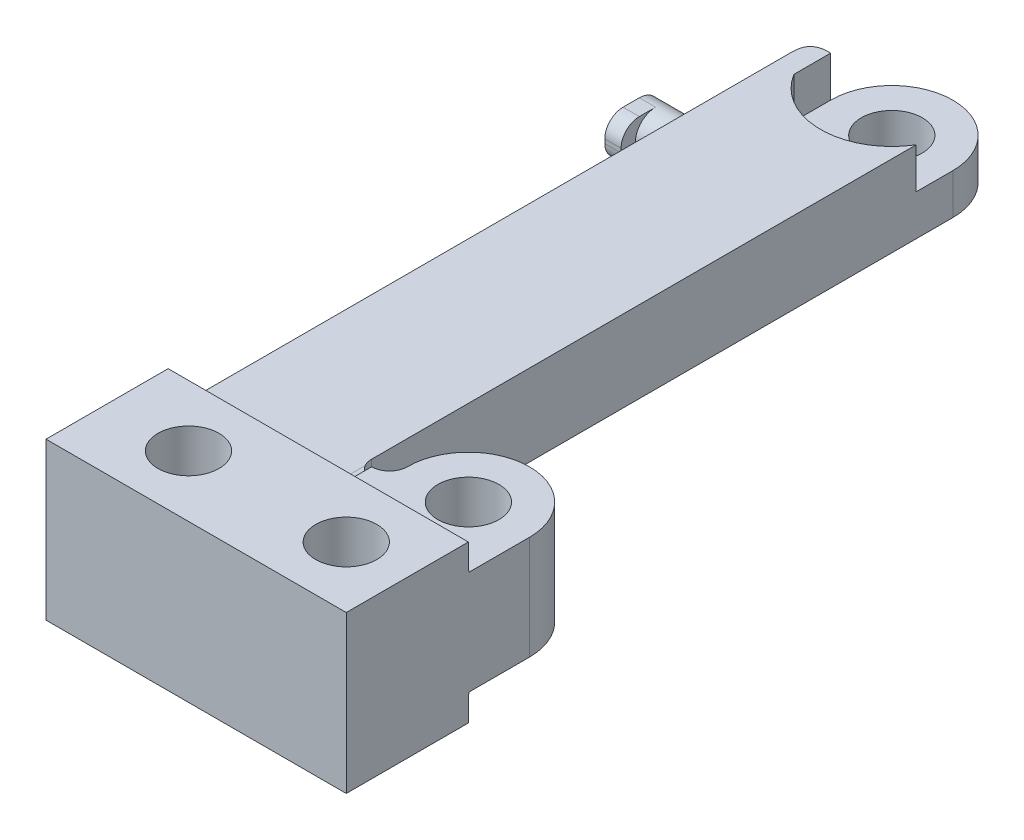
SolidWorks part; units mm, degrees
ref_plane "Front Plane" through (0, 0, 0) normal (0, 0, 1) x (1, 0, 0)
ref_plane "Top Plane" through (0, 0, 0) normal (0, 1, 0) x (1, 0, 0)
ref_plane "Right Plane" through (0, 0, 0) normal (1, 0, 0) x (0, 0, -1)
sketch "Sketch2" plane through (0, 0, 0) normal (0, 1, 0) x (1, 0, 0)
  line L0 (-6.875, 0) -> (6.875, 0)
  line L1 (-6.875, -6) -> (6.875, -6)
  line L2 (-6.875, -6) -> (-6.875, 6)
  line L5 (-6.875, -6) -> (6.875, 6) construction
  line L6 (-6.875, 6) -> (6.875, -6) construction
  line L7 (-0.875, 6) -> (-0.875, 31.55)
  line L9 (-6.875, 31.55) -> (-6.875, 6)
  line L10 (0, -8.1975) -> (0, 6) construction
  line L11 (6.875, 6) -> (-0.875, 6) construction
  line L12 (-3.875, -3) -> (-3.875, 34.55) construction
  line L13 (-0.875, 3) -> (-0.875, 6)
  line L14 (6.875, 3) -> (-0.875, 3) construction
  line L15 (6.875, 3) -> (6.875, -6)
  line L16 (6.875, 3) -> (6.875, 6) construction
  line L17 (0, 0) -> (0, 2.125)
  circle A4 centre (3.875, -3) radius 1.5
  circle A5 centre (3.875, 3) radius 1.5
  circle A6 centre (-3.875, -3) radius 1.5
  circle A7 centre (-3.875, 31.55) radius 1.5
  arc A8 (-6.875, 31.55) -> (-0.875, 31.55) centre (-3.875, 31.55) cw
  arc A9 (6.875, 3) -> (0.875, 3) centre (3.875, 3) ccw
  arc A10 (0.875, 3) -> (-0.875, 3) centre (0, 3) cw
  point P0 (0, 0)
  dimension "D3" = 3
  dimension "D4" = 3
  dimension "D8" = 3
  dimension "D1" = 13.75
  dimension "D2" = 12
  dimension "D5" = 3
  dimension "D6" = 3
  dimension "D7" = 7.75
  dimension "D9" = 34.55
extrude "Boss-Extrude1" add sketch "Sketch2" along normal mid plane 7.7 contours L15 L0 L2 L1 A6 A4 region at (0, 0, 3)
extrude "Boss-Extrude2" add sketch "Sketch2<4>" along normal mid plane 4 contours L17 A10 L13 L7 A8 L9 L2 L0 A7 region at (-3.8401, 0, -16.2788)
sketch "Sketch2<4>" plane through (0, 0, 0) normal (0, 1, 0) x (1, 0, 0) same geometry as "Sketch2"
extrude "Boss-Extrude3" add sketch "Sketch2<6>" along normal mid plane 5.1 contours A9 A10 L17 L0 L15 A5 region at (0.0912, 0, -1.0625)
sketch "Sketch2<6>" plane through (0, 0, 0) normal (0, 1, 0) x (1, 0, 0) same geometry as "Sketch2"
sketch "Sketch3" plane through (0, 2, 0) normal (0, 1, 0) x (1, 0, 0)
  line L0 (-6.875, 28.05) -> (-0.875, 28.05) construction
  line L1 (-6.875, 31.55) -> (-6.875, 0) construction
  line L2 (-0.875, 3) -> (-0.875, 31.55) construction
  line L3 (-6.875, 28.05) -> (-6.875, 31.55) construction
  line L4 (-0.875, 31.55) -> (-0.875, 28.05) construction
  line L5 (-6.875, 29.7472) -> (-6.875, 31.55)
  line L6 (-0.875, 29.7472) -> (-0.875, 31.55)
  circle A0 centre (-3.875, 31.55) radius 1.5 construction
  arc A1 (-6.875, 31.55) -> (-0.875, 31.55) centre (-3.875, 31.55) cw
  arc A2 (-0.875, 31.55) -> (-6.875, 31.55) centre (-3.875, 31.55) ccw construction
  arc A3 (-0.875, 29.7472) -> (-6.875, 29.7472) centre (-3.875, 31.55) cw
  dimension "D1" = 3.5
extrude "Cut-Extrude1" cut sketch "Sketch3" against normal blind 2
fillet "Fillet1" radius 0.8 2 edges at (-3.4375, -2, 0) (-3.4375, 2, 0)
fillet "Fillet2" radius 0.8 2 edges at (0, 2, -1.4625) (0, -2, -1.4625)
sketch "Sketch5" plane through (-6.875, 0, 0) normal (-1, 0, 0) x (0, 0, 1)
  line L0 (0, -3.85) -> (0, -2.8)
  line L1 (-0.8, -2) -> (-31.55, -2)
  line L2 (-29.7472, 2) -> (-20.7248, 2) construction
  line L3 (-31.55, -2) -> (-31.55, 2)
  line L4 (-31.55, 2) -> (-0.8, 2)
  line L5 (0, -3.85) -> (6, -3.85)
  line L6 (6, -3.85) -> (6, 3.85)
  line L7 (6, 3.85) -> (0, 3.85)
  line L8 (0, 3.85) -> (0, 2.8)
  line L9 (-31.55, -2.662) -> (-31.55, 3.85) construction
  arc A0 (0, 2.8) -> (-0.8, 2) centre (-0.8, 2.8) cw
  arc A1 (-0.8, -2) -> (0, -2.8) centre (-0.8, -2.8) cw
extrude "Boss-Extrude4" add sketch "Sketch5" along normal blind 1
fillet "Fillet4" radius 1 1 edges at (-7.875, 0, -31.55) curvature continuous yes
sketch "Sketch6" plane through (-7.875, 0, 0) normal (-1, 0, 0) x (0, 0, 1)
  line L0 (-34.55, 1.687) -> (-34.55, -3.8532) construction
  line L1 (-31.55, 2) -> (-31.55, -3.8532) construction
  line L2 (-28.55, 1.687) -> (-28.55, -3.8532) construction
  line L3 (-21.9328, 0) -> (-0.3669, 0) construction
  circle A0 centre (-25.95, 0) radius 1
  dimension "D1" = 2
  dimension "D2" = 6
  dimension "D3" = 2.6
extrude "Boss-Extrude5" add sketch "Sketch6" along normal blind 2
sketch "Sketch7" plane through (-9.875, 0, 0) normal (-1, 0, 0) x (0, 0, 1)
  line L0 (-25.95, 1) -> (-25.15, 1)
  line L1 (-24.25, 0.1) -> (-24.25, -0.1)
  line L2 (-25.15, -1) -> (-25.95, -1)
  line L3 (-30.55, 2) -> (-30.55, -2) construction
  circle A0 centre (-25.95, 0) radius 1 construction
  circle A1 centre (-25.95, 0) radius 1 construction
  arc A2 (-25.15, -1) -> (-24.25, -0.1) centre (-25.15, -0.1) ccw
  arc A3 (-25.15, 1) -> (-24.25, 0.1) centre (-25.15, 0.1) cw
  arc A4 (-25.95, 1) -> (-25.95, -1) centre (-25.95, 0) ccw
  circle M4 centre (-25.95, 0) radius 1
  dimension "D1" = 0.9
  dimension "D3" = 4.6
  dimension "D2" = 0.8
extrude "Boss-Extrude6" add sketch "Sketch7" along normal blind 0.8 contours A3 L0 L2 A2 L1 M4 | M4 region at (-9.875, 0, -25.95) region at (-9.875, 0, -24.8011)
